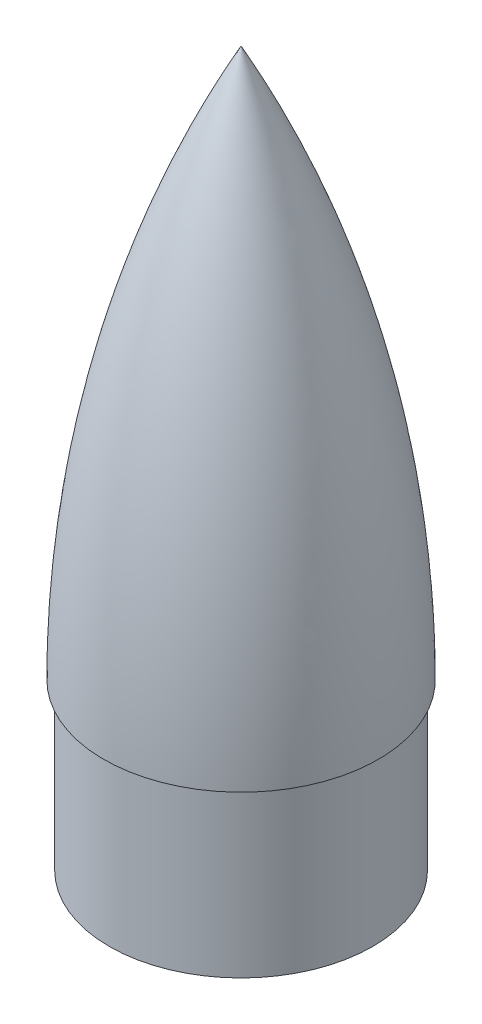
SolidWorks part; units mm, degrees
ref_plane "Спереди" through (0, 0, 0) normal (0, 0, 1) x (1, 0, 0)
ref_plane "Сверху" through (0, 0, 0) normal (0, 1, 0) x (1, 0, 0)
ref_plane "Справа" through (0, 0, 0) normal (1, 0, 0) x (0, 0, -1)
sketch "Эскиз1" plane through (0, 0, 0) normal (0, 0, 1) x (1, 0, 0)
  line L0 (0, 0) -> (0, 303.0776) construction
  line L1 (-239.649, 0) -> (394.9518, 0) construction
  line L3 (-25, 0) -> (-24, 0)
  line L4 (0, 100) -> (0, -30)
  line L5 (0, -30) -> (-24, -30)
  line L6 (-24, 0) -> (-24, -30)
  arc A0 (0, 100) -> (-25, 0) centre (187.5, 0) ccw
  point P2 (0, 100)
  point P4 (0, 0)
  dimension "D1" = 425
  dimension "D3" = 30
  dimension "D4" = 1
  dimension "D2" = 24
revolve "Повернуть1" add sketch "Эскиз1" angle 360 about L4
shell "Оболочка2" thickness 1.2 removed face at (-24, -30, 0)
